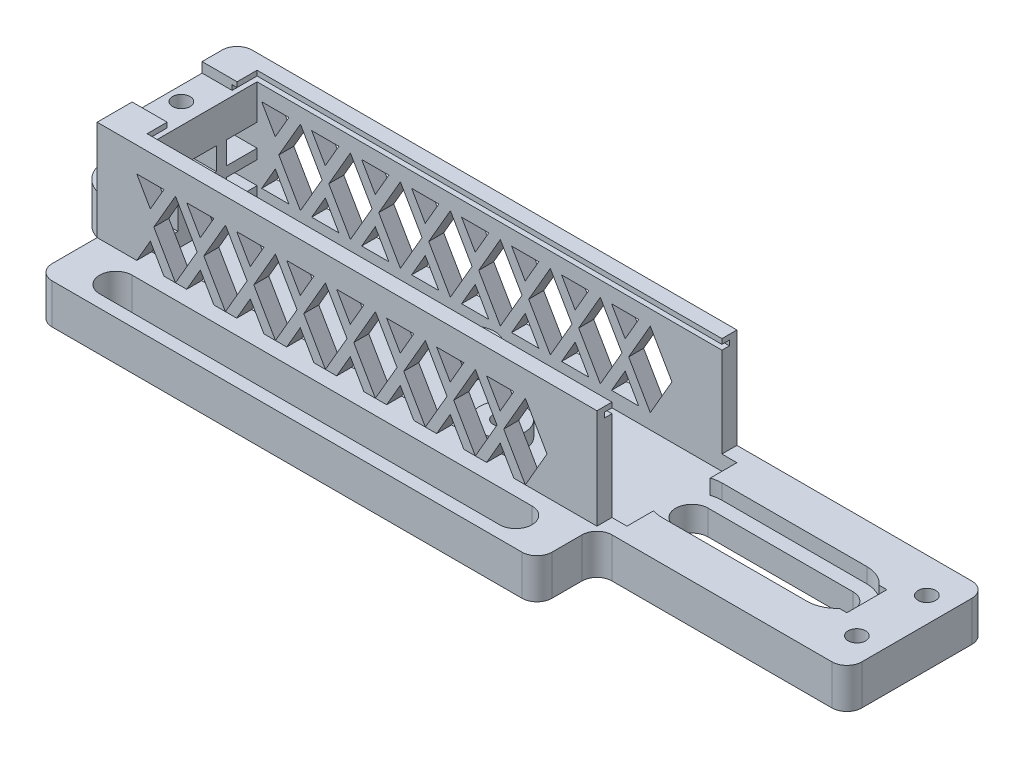
SolidWorks part; units mm, degrees
ref_plane "Ebene vorne" through (0, 0, 0) normal (0, 0, 1) x (1, 0, 0)
ref_plane "Ebene oben" through (0, 0, 0) normal (0, 1, 0) x (1, 0, 0)
ref_plane "Ebene rechts" through (0, 0, 0) normal (1, 0, 0) x (0, 0, -1)
sketch "Skizze1" plane through (0, 0, 0) normal (0, 1, 0) x (1, 0, 0)
  line L1 (-50, -20) -> (50, -20)
  line L2 (-50, -20) -> (-50, 20)
  line L3 (-50, 20) -> (50, 20)
  line L4 (50, -20) -> (50, 20)
  line L5 (-50, -20) -> (50, 20) construction
  line L6 (-50, 20) -> (50, -20) construction
  point P0 (0, 0)
  dimension "D1" = 100
  dimension "D2" = 40
extrude "Aufsatz-Linear austragen1" add sketch "Skizze1" along normal blind 8
sketch "Skizze2" plane through (0, 8, 0) normal (0, 1, 0) x (1, 0, 0)
  line L0 (50, -20) -> (50, 20) construction
  line L1 (50, 17) -> (27, 17)
  line L2 (50, 17) -> (50, -5)
  line L3 (50, -5) -> (27, -5)
  line L4 (27, 17) -> (27, -5)
  line L5 (50, 20) -> (-50, 20) construction
  line L7 (-31, 11) -> (-24, 11)
  line L8 (-31, 11) -> (-31, 1)
  line L9 (-31, 1) -> (-24, 1)
  line L10 (-24, 11) -> (-24, 1)
  dimension "D1" = 23
  dimension "D2" = 22
  dimension "D3" = 3
  dimension "D4" = 81
  dimension "D5" = 7
  dimension "D6" = 6
  dimension "D7" = 6
extrude "Schnitt-Linear austragen1" cut sketch "Skizze2" against normal blind 3
sketch "Skizze4" plane through (0, 8, 0) normal (0, 1, 0) x (1, 0, 0)
  line L0 (50, 17) -> (27, 17) construction
  line L1 (-31, 11) -> (-31, 1) construction
  circle A0 centre (6, 11) radius 1.75
  circle A1 centre (22, 1) radius 1.75
  dimension "D1" = 3.5
  dimension "D2" = 3.5
  dimension "D6" = 37
  dimension "D3" = 10
  dimension "D4" = 16
  dimension "D5" = 6
extrude "Schnitt-Linear austragen2" cut sketch "Skizze4" against normal through all
sketch "Skizze5" plane through (0, 0, 0) normal (0, -1, 0) x (1, 0, 0)
  line L1 (2.7091, -11) -> (4.3546, -13.85)
  line L2 (4.3546, -13.85) -> (7.6454, -13.85)
  line L3 (7.6454, -13.85) -> (9.2909, -11)
  line L4 (9.2909, -11) -> (7.6454, -8.15)
  line L5 (7.6454, -8.15) -> (4.3546, -8.15)
  line L6 (4.3546, -8.15) -> (2.7091, -11)
  line L7 (18.7091, -1) -> (20.3546, -3.85)
  line L8 (20.3546, -3.85) -> (23.6454, -3.85)
  line L9 (23.6454, -3.85) -> (25.2909, -1)
  line L10 (25.2909, -1) -> (23.6454, 1.85)
  line L11 (23.6454, 1.85) -> (20.3546, 1.85)
  line L12 (20.3546, 1.85) -> (18.7091, -1)
  circle A0 centre (6, -11) radius 2.85 construction
  circle A1 centre (22, -1) radius 2.85 construction
  dimension "D1" = 5.7
  dimension "D2" = 5.7
extrude "Schnitt-Linear austragen3" cut sketch "Skizze5" against normal blind 3
sketch "Skizze6" plane through (0, 8, 0) normal (0, 1, 0) x (1, 0, 0)
  line L0 (50, 17) -> (50, 20)
  line L1 (50, 20) -> (-50, 20)
  line L2 (-50, 20) -> (-50, -8)
  line L3 (-50, 20) -> (-50, -20) construction
  line L4 (-50, -8) -> (50, -8)
  line L5 (50, -20) -> (50, -5) construction
  line L6 (50, -8) -> (50, -5)
  line L7 (50, -5) -> (-43, -5)
  line L8 (-43, -5) -> (-43, 17)
  line L9 (-43, 17) -> (50, 17)
  dimension "D1" = 3
  dimension "D2" = 7
extrude "Aufsatz-Linear austragen2" add sketch "Skizze6" along normal blind 20
sketch "Skizze7" plane through (0, 0, -20) normal (0, 0, -1) x (-1, 0, 0)
  line L0 (-35.6699, 23) -> (-40, 15.5)
  line L1 (-40, 15.5) -> (-35.6699, 8)
  line L2 (-35.6699, 8) -> (-31.3397, 15.5)
  line L3 (-31.3397, 15.5) -> (-35.6699, 23)
  line L4 (-50, 28) -> (50, 28) construction
  line L5 (-50, 0) -> (50, 0) construction
  line L6 (-50, 28) -> (-50, 0) construction
  line L7 (-33.3605, 8) -> (-30.6397, 12.7124)
  line L8 (-30.6397, 12.7124) -> (-27.919, 8)
  line L9 (-27.919, 8) -> (-33.3605, 8)
  line L10 (-33.3605, 23) -> (-30.6397, 18.2876)
  line L11 (-30.6397, 18.2876) -> (-27.919, 23)
  line L12 (-27.919, 23) -> (-33.3605, 23)
  dimension "D1" = 60
  dimension "D2" = 60
  dimension "D3" = 5
  dimension "D4" = 8
  dimension "D5" = 0
  dimension "D6" = 0
  dimension "D7" = 10
  dimension "D8" = 2
  dimension "D9" = 0
  dimension "D10" = 60
  dimension "D11" = 2
  dimension "D12" = 60
  dimension "D13" = 0.7
  dimension "D14" = 0.7
extrude "Schnitt-Linear austragen4" cut sketch "Skizze7" against normal through all
pattern_linear "Lineares Muster1" count 8 spacing 10 along (-1, 0, 0) of "Schnitt-Linear austragen4"
sketch "Skizze9" plane through (50, 0, 0) normal (1, 0, 0) x (0, 0, -1)
  line L0 (-5, 5) -> (-5, 28) construction
  line L1 (-6.5, 27) -> (18.5, 27)
  line L2 (-6.5, 27) -> (-6.5, 26)
  line L3 (-6.5, 26) -> (18.5, 26)
  line L4 (18.5, 27) -> (18.5, 26)
  line L5 (20, 28) -> (20, 0) construction
  line L6 (17, 28) -> (20, 28) construction
  dimension "D1" = 1.5
  dimension "D2" = 1.5
  dimension "D3" = 1
  dimension "D4" = 1
extrude "Schnitt-Linear austragen5" cut sketch "Skizze9" against normal offset from surface (94 mm away) 1 up to face at (-43, 18, -6) offset beyond the face yes
sketch "Skizze10" plane through (0, 28, 0) normal (0, 1, 0) x (1, 0, 0)
  line L0 (-50, 20) -> (-50, -8) construction
  line L1 (-50, 13) -> (-43, 13)
  line L2 (-50, 13) -> (-50, -1)
  line L3 (-50, -1) -> (-43, -1)
  line L4 (-43, 13) -> (-43, -1)
  line L5 (-43, -5) -> (-43, 17) construction
  line L6 (-43, 17) -> (50, 17) construction
  dimension "D1" = 4
  dimension "D2" = 4
extrude "Schnitt-Linear austragen6" cut sketch "Skizze10" against normal up to surface (2 mm away) up to face at (3.25, 26, -6)
sketch "Skizze11" plane through (0, 26, 0) normal (0, 1, 0) x (1, 0, 0)
  line L1 (-44.3, 4.3546) -> (-44.3, 7.6454)
  line L2 (-44.3, 7.6454) -> (-46.3863, 8.85)
  line L3 (-50, 3.15) -> (-46.3863, 3.15)
  line L4 (-50, 8.85) -> (-50, 3.15)
  line L5 (-46.3863, 8.85) -> (-50, 8.85)
  line L6 (-46.3863, 3.15) -> (-44.3, 4.3546)
  line L7 (-43, 17) -> (50, 17) construction
  line L8 (-50, 13) -> (-50, -1) construction
  line L9 (-47.15, 9.2909) -> (-50, 7.6454) [skipped]
  line L10 (-50, 4.3546) -> (-47.15, 2.7091) [skipped]
  circle A0 centre (-47.15, 6) radius 2.85 construction
  dimension "D1" = 2.85
  dimension "D2" = 11
  dimension "D3" = 0
  dimension "D4" = 0
  dimension "D5" = 5.7
extrude "Schnitt-Linear austragen7" cut sketch "Skizze11" against normal blind 3 from offset 3 offset against normal yes
sketch "Skizze12" plane through (0, 23, 0) normal (0, -1, 0) x (1, 0, 0)
  line L0 (-44.3, -7.6454) -> (-46.3863, -8.85) construction
  line L1 (-46.3863, -3.15) -> (-44.3, -4.3546) construction
  circle A0 centre (-47.15, -6) radius 1.75
  dimension "D3" = 3.5
  dimension "D1" = 2.85
  dimension "D2" = 2.85
extrude "Schnitt-Linear austragen8" cut sketch "Skizze12" against normal blind 3 and the other way blind 8
sketch "Skizze13" plane through (-50, 0, 0) normal (-1, 0, 0) x (0, 0, 1)
  line L0 (8, 8) -> (20, 8) construction
  line L1 (-17, 19) -> (-10.85, 19)
  line L2 (-17, 19) -> (-17, 14.5)
  line L3 (-17, 14.5) -> (-10.85, 14.5)
  line L4 (-10.85, 19) -> (-10.85, 14.5)
  line L5 (-17, 12.5) -> (-10.85, 12.5)
  line L6 (-17, 12.5) -> (-17, 8)
  line L7 (-17, 8) -> (-10.85, 8)
  line L8 (-10.85, 12.5) -> (-10.85, 8)
  line L9 (-20, 28) -> (-20, 0) construction
  line L13 (5, 19) -> (-1.15, 19)
  line L14 (5, 19) -> (5, 14.5)
  line L15 (5, 14.5) -> (-1.15, 14.5)
  line L16 (-1.15, 19) -> (-1.15, 14.5)
  line L17 (-8.85, 20) -> (-8.85, 23) construction
  line L18 (5, 12.5) -> (-1.15, 12.5)
  line L19 (5, 12.5) -> (5, 8)
  line L20 (5, 8) -> (-1.15, 8)
  line L21 (-1.15, 12.5) -> (-1.15, 8)
  line L22 (-8.85, 19) -> (-3.15, 19)
  line L23 (-8.85, 19) -> (-8.85, 14.5)
  line L24 (-8.85, 14.5) -> (-3.15, 14.5)
  line L25 (-3.15, 19) -> (-3.15, 14.5)
  line L26 (-8.85, 12.5) -> (-3.15, 12.5)
  line L27 (-8.85, 12.5) -> (-8.85, 8)
  line L28 (-8.85, 8) -> (-3.15, 8)
  line L29 (-3.15, 12.5) -> (-3.15, 8)
  line L30 (-3.15, 20) -> (-3.15, 23) construction
  line L31 (8, 28) -> (8, 8) construction
  dimension "D1" = 0
  dimension "D2" = 3
  dimension "D3" = 2
  dimension "D4" = 1
  dimension "D5" = 2
  dimension "D6" = 0
  dimension "D7" = 0
  dimension "D8" = 4.5
  dimension "D9" = 2
  dimension "D10" = 0
  dimension "D11" = 0
  dimension "D12" = 0
  dimension "D13" = 0
  dimension "D14" = 0
  dimension "D15" = 3
  dimension "D16" = 3
extrude "Schnitt-Linear austragen9" cut sketch "Skizze13" against normal up to surface (7 mm away) up to face at (-43, 17, -6)
sketch "Skizze14" plane through (0, 8, 0) normal (0, 1, 0) x (1, 0, 0)
  line L0 (-40, -14.25) -> (40, -14.25) construction
  line L1 (-40, -11) -> (40, -11)
  line L2 (-40, -17.5) -> (40, -17.5)
  line L3 (-50, -20) -> (50, -20) construction
  line L4 (50, -20) -> (50, -8) construction
  line L5 (-50, -8) -> (-50, -20) construction
  arc A0 (-40, -11) -> (-40, -17.5) centre (-40, -14.25) ccw
  arc A1 (40, -17.5) -> (40, -11) centre (40, -14.25) ccw
  point P2 (0, -14.25)
  dimension "D1" = 6.5
  dimension "D2" = 2.5
  dimension "D3" = 10
  dimension "D4" = 10
extrude "Schnitt-Linear austragen10" cut sketch "Skizze14" against normal through all
sketch "Skizze15" plane through (50, 0, 0) normal (1, 0, 0) x (0, 0, -1)
  line L0 (-8, 8) -> (-8, 0)
  line L1 (-20, 0) -> (20, 0) construction
  line L2 (-8, 0) -> (20, 0)
  line L3 (20, 0) -> (20, 8)
  line L4 (20, 28) -> (20, 0) construction
  line L5 (20, 8) -> (10, 8)
  line L6 (17, 8) -> (-5, 8) construction
  line L7 (10, 8) -> (10, 5)
  line L8 (-5, 5) -> (17, 5) construction
  line L9 (10, 5) -> (2, 5)
  line L10 (17, 5) -> (-5, 5) construction
  line L11 (2, 5) -> (2, 8)
  line L12 (2, 8) -> (-8, 8)
  point P5 (6, 0)
  dimension "D1" = 0
  dimension "D2" = 8
  dimension "D3" = 4
extrude "Aufsatz-Linear austragen3" add sketch "Skizze15" along normal blind 50
sketch "Skizze16" plane through (100, 0, 0) normal (1, 0, 0) x (0, 0, -1)
  line L1 (2, 8) -> (10, 8)
  line L2 (2, 8) -> (2, 5)
  line L3 (2, 5) -> (10, 5)
  line L4 (10, 8) -> (10, 5)
extrude "Aufsatz-Linear austragen4" add sketch "Skizze16" against normal blind 10
sketch "Skizze17" plane through (0, 8, 0) normal (0, 1, 0) x (1, 0, 0)
  line L0 (100, 20) -> (100, -8) construction
  line L1 (100, -8) -> (50, -8) construction
  line L2 (100, 20) -> (50, 20) construction
  circle A0 centre (95, 13) radius 1.75
  circle A1 centre (95, -1) radius 1.75
  dimension "D3" = 7
  dimension "D4" = 7
  dimension "D5" = 3.5
  dimension "D6" = 3.5
  dimension "D1" = 5
  dimension "D2" = 5
extrude "Schnitt-Linear austragen11" cut sketch "Skizze17" against normal through all
sketch "Skizze18" plane through (0, 0, 0) normal (0, -1, 0) x (1, 0, 0)
  line L1 (92.3866, -1.0001) -> (95.4254, -2.2633)
  line L2 (95.4254, -2.2633) -> (98.0388, -0.2632)
  line L3 (98.0388, -0.2632) -> (97.6134, 3.0001)
  line L4 (97.6134, 3.0001) -> (94.5746, 4.2633)
  line L5 (94.5746, 4.2633) -> (91.9612, 2.2632)
  line L6 (91.9612, 2.2632) -> (92.3866, -1.0001)
  line L7 (97.85, -14.6454) -> (97.85, -11.3546)
  line L8 (97.85, -11.3546) -> (95, -9.7091)
  line L9 (95, -9.7091) -> (92.15, -11.3546)
  line L10 (92.15, -11.3546) -> (92.15, -14.6454)
  line L11 (92.15, -14.6454) -> (95, -16.2909)
  line L12 (95, -16.2909) -> (97.85, -14.6454)
  line L13 (100, 8) -> (100, -20) construction
  circle A0 centre (95, 1) radius 2.85 construction
  circle A1 centre (95, -13) radius 2.85 construction
  dimension "D1" = 5.7
  dimension "D2" = 5.7
  dimension "D3" = 180
extrude "Schnitt-Linear austragen12" cut sketch "Skizze18" against normal blind 3
fillet "Verrundung1" radius 3 6 edges at (-50, 14, -20) (-50, 4, 20) (100, 4, -20) (100, 4, 8) (50, 4, 20)
sketch "Skizze19" plane through (0, 8, 0) normal (0, 1, 0) x (1, 0, 0)
  line L0 (-43, 17) -> (50, 17) construction
  line L1 (-43, -5) -> (53, -5)
  line L2 (-43, -5) -> (-43, 17)
  line L3 (-43, 17) -> (53, 17)
  line L4 (53, -5) -> (53, 17)
  line L5 (50, 17) -> (50, 10) construction
  circle A0 centre (6, 11) radius 4.5
  circle A1 centre (22, 1) radius 4.5
  dimension "D3" = 9
  dimension "D4" = 9
  dimension "D1" = 0
  dimension "D2" = 3
extrude "Schnitt-Linear austragen13" cut sketch "Skizze19" against normal blind 3
sketch "Skizze20" plane through (0, 8, 0) normal (0, 1, 0) x (1, 0, 0)
  line L0 (-50, 13) -> (-50, -1) construction
  line L1 (-56.25, 12.25) -> (-50, 12.25)
  line L2 (-50, 12.25) -> (-50, -0.25)
  line L3 (-50, -0.25) -> (-56.25, -0.25)
  circle A0 centre (-56.25, 6) radius 3.25
  circle A3 centre (-47.15, 6) radius 1.75 construction
  arc A4 (-56.25, 12.25) -> (-56.25, -0.25) centre (-56.25, 6) ccw
  dimension "D1" = 6.5
  dimension "D2" = 0
  dimension "D3" = 6.25
  dimension "D7" = 0
  dimension "D8" = 3
  dimension "D4" = 0
  dimension "D5" = 0
  dimension "D6" = 0
extrude "Aufsatz-Linear austragen5" add sketch "Skizze20" against normal up to surface (8 mm away) up to face at (95, 0, -13)
sketch "Skizze21" plane through (0, 5, 0) normal (0, 1, 0) x (1, 0, 0)
  line L0 (55, 6) -> (84, 6) construction
  line L1 (55, 9.25) -> (84, 9.25)
  line L2 (55, 2.75) -> (84, 2.75)
  line L3 (90, 10) -> (53, 10) construction
  line L4 (50, 20) -> (50, 17) construction
  line L5 (90, 10) -> (90, 2) construction
  arc A0 (55, 9.25) -> (55, 2.75) centre (55, 6) ccw
  arc A1 (84, 2.75) -> (84, 9.25) centre (84, 6) ccw
  point P2 (69.5, 6)
  dimension "D1" = 6.5
  dimension "D2" = 4
  dimension "D3" = 5
  dimension "D4" = 6
extrude "Schnitt-Linear austragen14" cut sketch "Skizze21" against normal through all
sketch "Skizze22" plane through (0, 5, 0) normal (0, 1, 0) x (1, 0, 0)
  line L0 (55, 6) -> (84, 6) construction
  line L1 (55, 12) -> (84, 12)
  line L2 (55, 0) -> (84, 0)
  arc A0 (55, 12) -> (55, 0) centre (55, 6) ccw
  arc A1 (84, 0) -> (84, 12) centre (84, 6) ccw
  point P4 (69.5, 6)
  dimension "D1" = 12
extrude "Schnitt-Linear austragen16" cut sketch "Skizze22" along normal up to surface (3 mm away) up to face at (-8.6801, 8, -18.5)
